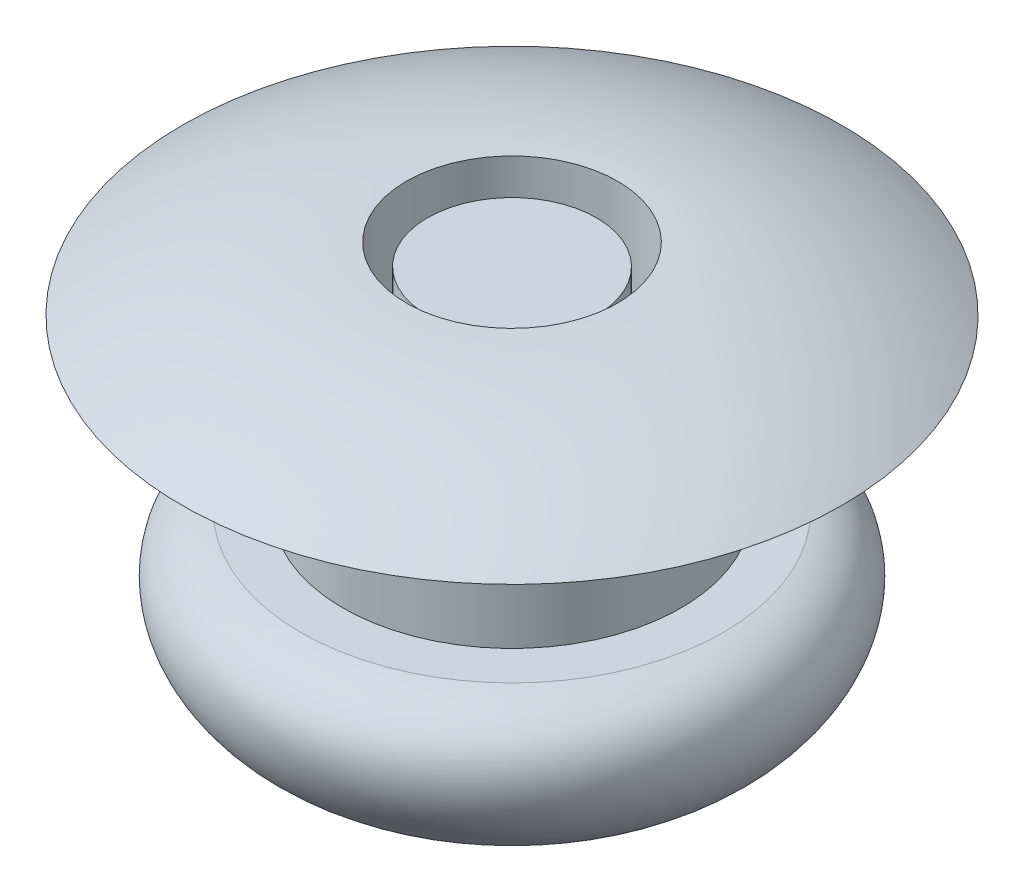
SolidWorks part; units mm, degrees
material "AISI 316 Arkusz stali nierdzewnej (SS)"
ref_plane "Płaszczyzna przednia" through (0, 0, 0) normal (0, 0, 1) x (1, 0, 0)
ref_plane "Płaszczyzna górna" through (0, 0, 0) normal (0, 1, 0) x (1, 0, 0)
ref_plane "Płaszczyzna prawa" through (0, 0, 0) normal (1, 0, 0) x (0, 0, -1)
sketch "Szkic1" plane through (0, 0, 0) normal (0, 0, 1) x (1, 0, 0)
  line L0 (0, 0) -> (0, 0.724) construction
  line L1 (-3.9, 4) -> (-2, 4)
  line L2 (-1.25, 4.75) -> (-1.25, 2)
  line L3 (-2, 4) -> (-2, 2)
  line L4 (-1.25, 2) -> (-1, 2)
  line L5 (-1, 2) -> (-1, 4.5)
  line L6 (-1, 4.5) -> (0, 4.5)
  line L7 (-2, 2) -> (-2.5, 2)
  line L8 (0, 0) -> (0, 0.5785) construction
  line L9 (0, 4.5) -> (0, 0.5785) construction
  line L10 (0, 4.5) -> (0, 0.5785)
  line L11 (3.75, 4) -> (-12.25, 4) construction
  line L15 (8.75, 2) -> (-17.25, 2) construction
  arc A0 (-1.25, 4.75) -> (-3.9, 4) centre (-1.25, -0.3067) ccw
  spline S0 degree 3 poles (-2.5, 2) (-3.3276, 1.8522) (-3.2549, 0.0346) (-0.0301, -0.3768) (-1.229, 1.675) (-0.2169, 0.5088) (0, 0.5785) knots 0 0 0 0 0.343812 0.687239 0.819799 1 1 1 1
  point P7 (-1.25, -4.3067)
  dimension "D1" = 7.8
  dimension "D2" = 0.75
  dimension "D3" = 4
  dimension "D4" = 2.5
  dimension "D5" = 0.5
  dimension "D6" = 2
  dimension "D7" = 5
  dimension "D8" = 1.5978
  dimension "D9" = 0.3519
  dimension "D10" = 1.5835
  dimension "D11" = 1.2582
  dimension "D12" = 1.4215
  dimension "D13" = 0.8591
  dimension "D14" = 0.7171
  dimension "D15" = 1.256
  dimension "D16" = 1.715
  dimension "D17" = 5.1929
  dimension "D18" = 6.0862
revolve "Obrót1" add sketch "Szkic1" angle 360 about L9
